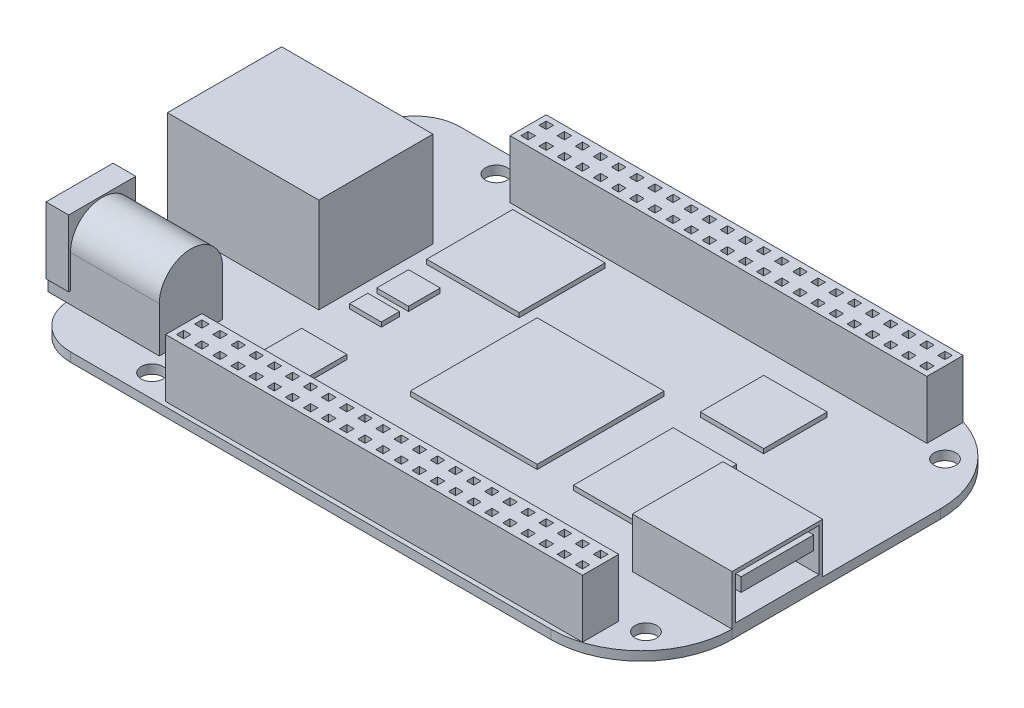
SolidWorks part; units mm, degrees
material "ABS"
ref_plane "Front Plane" through (0, 0, 0) normal (0, 0, 1) x (1, 0, 0)
ref_plane "Top Plane" through (0, 0, 0) normal (0, 1, 0) x (1, 0, 0)
ref_plane "Right Plane" through (0, 0, 0) normal (1, 0, 0) x (0, 0, -1)
sketch "Sketch1" plane through (0, 0, 0) normal (0, 1, 0) x (1, 0, 0)
  line L1 (-12.7, 0) -> (-80.01, 0)
  line L2 (0, 12.7) -> (0, 41.91)
  line L3 (-12.7, 54.61) -> (-80.01, 54.61)
  line L4 (-86.36, 6.35) -> (-86.36, 48.26)
  arc A0 (0, 12.7) -> (-12.7, 0) centre (-12.7, 12.7) cw
  arc A1 (0, 41.91) -> (-12.7, 54.61) centre (-12.7, 41.91) ccw
  arc A2 (-86.36, 6.35) -> (-80.01, 0) centre (-80.01, 6.35) ccw
  arc A3 (-86.36, 48.26) -> (-80.01, 54.61) centre (-80.01, 48.26) cw
  point P7 (0, 0)
  point P10 (0, 54.61)
  point P13 (-86.36, 0)
  dimension "D3" = 12.7
  dimension "D4" = 6.35
  dimension "D1" = 86.36
  dimension "D2" = 54.61
extrude "Boss-Extrude1" add sketch "Sketch1" along normal blind 1.27
sketch "Sketch2" plane through (0, 1.27, 0) normal (0, 1, 0) x (1, 0, 0)
  line L0 (-80.01, 0) -> (-12.7, 0) construction
  line L2 (-71.755, 51.435) -> (-71.755, 3.175) construction
  line L3 (-86.36, 48.26) -> (-86.36, 6.35) construction
  line L4 (-5.715, 48.26) -> (-5.715, 6.35) construction
  circle A0 centre (-71.755, 51.435) radius 1.524
  circle A1 centre (-71.755, 3.175) radius 1.524
  circle A2 centre (-5.715, 48.26) radius 1.524
  circle A3 centre (-5.715, 6.35) radius 1.524
  point P10 (-13.1534, 1.6759)
  point P15 (-61.1926, 0)
  dimension "D7" = 3.048
  dimension "D1" = 48.26
  dimension "D2" = 41.91
  dimension "D3" = 6.35
  dimension "D4" = 14.605
  dimension "D5" = 80.645
  dimension "D6" = 3.175
extrude "Cut-Extrude1" cut sketch "Sketch2" along direction (0, -1, 0) on the side against the normal up to surface (1.27 mm away) up to face at (-44.4387, 0, -27.305)
sketch "Sketch3" plane through (0, 1.27, 0) normal (0, 1, 0) x (1, 0, 0)
  line L0 (-10.16, 48.895) -> (-10.16, 50.165) construction
  line L1 (-67.31, 53.975) -> (-8.89, 53.975)
  line L2 (-67.31, 53.975) -> (-67.31, 48.895)
  line L3 (-67.31, 48.895) -> (-8.89, 48.895)
  line L4 (-8.89, 53.975) -> (-8.89, 48.895)
  line L5 (-86.36, 27.305) -> (0, 27.305) construction
  line L6 (0, 12.7) -> (0, 41.91) construction
  line L7 (-66.548, 4.953) -> (-66.548, 3.937)
  line L8 (-66.548, 4.953) -> (-65.532, 4.953)
  line L9 (-10.16, 50.165) -> (-10.16, 52.705) construction
  line L10 (-10.16, 52.705) -> (-10.16, 53.975) construction
  line L11 (-13.208, 52.197) -> (-12.192, 52.197)
  line L12 (-10.668, 53.213) -> (-9.652, 53.213)
  line L13 (-10.668, 53.213) -> (-10.668, 52.197)
  line L14 (-10.668, 52.197) -> (-9.652, 52.197)
  line L15 (-9.652, 53.213) -> (-9.652, 52.197)
  line L16 (-10.668, 53.213) -> (-9.652, 52.197) construction
  line L17 (-10.668, 52.197) -> (-9.652, 53.213) construction
  line L18 (-10.668, 49.657) -> (-9.652, 49.657)
  line L19 (-10.668, 49.657) -> (-10.668, 50.673)
  line L20 (-10.668, 50.673) -> (-9.652, 50.673)
  line L21 (-9.652, 49.657) -> (-9.652, 50.673)
  line L22 (-10.668, 49.657) -> (-9.652, 50.673) construction
  line L23 (-10.668, 50.673) -> (-9.652, 49.657) construction
  line L24 (-13.208, 53.213) -> (-13.208, 52.197)
  line L25 (-13.208, 53.213) -> (-12.192, 53.213)
  line L26 (-12.192, 53.213) -> (-12.192, 52.197)
  line L27 (-13.208, 50.673) -> (-12.192, 50.673)
  line L28 (-12.192, 49.657) -> (-12.192, 50.673)
  line L29 (-13.208, 49.657) -> (-12.192, 49.657)
  line L30 (-13.208, 49.657) -> (-13.208, 50.673)
  line L31 (-15.748, 52.197) -> (-14.732, 52.197)
  line L32 (-15.748, 53.213) -> (-15.748, 52.197)
  line L33 (-15.748, 53.213) -> (-14.732, 53.213)
  line L34 (-14.732, 53.213) -> (-14.732, 52.197)
  line L35 (-15.748, 50.673) -> (-14.732, 50.673)
  line L36 (-14.732, 49.657) -> (-14.732, 50.673)
  line L37 (-15.748, 49.657) -> (-14.732, 49.657)
  line L38 (-15.748, 49.657) -> (-15.748, 50.673)
  line L39 (-18.288, 52.197) -> (-17.272, 52.197)
  line L40 (-18.288, 53.213) -> (-18.288, 52.197)
  line L41 (-18.288, 53.213) -> (-17.272, 53.213)
  line L42 (-17.272, 53.213) -> (-17.272, 52.197)
  line L43 (-18.288, 50.673) -> (-17.272, 50.673)
  line L44 (-17.272, 49.657) -> (-17.272, 50.673)
  line L45 (-18.288, 49.657) -> (-17.272, 49.657)
  line L46 (-18.288, 49.657) -> (-18.288, 50.673)
  line L47 (-20.828, 52.197) -> (-19.812, 52.197)
  line L48 (-20.828, 53.213) -> (-20.828, 52.197)
  line L49 (-20.828, 53.213) -> (-19.812, 53.213)
  line L50 (-19.812, 53.213) -> (-19.812, 52.197)
  line L51 (-20.828, 50.673) -> (-19.812, 50.673)
  line L52 (-19.812, 49.657) -> (-19.812, 50.673)
  line L53 (-20.828, 49.657) -> (-19.812, 49.657)
  line L54 (-20.828, 49.657) -> (-20.828, 50.673)
  line L55 (-23.368, 52.197) -> (-22.352, 52.197)
  line L56 (-23.368, 53.213) -> (-23.368, 52.197)
  line L57 (-23.368, 53.213) -> (-22.352, 53.213)
  line L58 (-22.352, 53.213) -> (-22.352, 52.197)
  line L59 (-23.368, 50.673) -> (-22.352, 50.673)
  line L60 (-22.352, 49.657) -> (-22.352, 50.673)
  line L61 (-23.368, 49.657) -> (-22.352, 49.657)
  line L62 (-23.368, 49.657) -> (-23.368, 50.673)
  line L63 (-25.908, 52.197) -> (-24.892, 52.197)
  line L64 (-25.908, 53.213) -> (-25.908, 52.197)
  line L65 (-25.908, 53.213) -> (-24.892, 53.213)
  line L66 (-24.892, 53.213) -> (-24.892, 52.197)
  line L67 (-25.908, 50.673) -> (-24.892, 50.673)
  line L68 (-24.892, 49.657) -> (-24.892, 50.673)
  line L69 (-25.908, 49.657) -> (-24.892, 49.657)
  line L70 (-25.908, 49.657) -> (-25.908, 50.673)
  line L71 (-28.448, 52.197) -> (-27.432, 52.197)
  line L72 (-28.448, 53.213) -> (-28.448, 52.197)
  line L73 (-28.448, 53.213) -> (-27.432, 53.213)
  line L74 (-27.432, 53.213) -> (-27.432, 52.197)
  line L75 (-28.448, 50.673) -> (-27.432, 50.673)
  line L76 (-27.432, 49.657) -> (-27.432, 50.673)
  line L77 (-28.448, 49.657) -> (-27.432, 49.657)
  line L78 (-28.448, 49.657) -> (-28.448, 50.673)
  line L79 (-30.988, 52.197) -> (-29.972, 52.197)
  line L80 (-30.988, 53.213) -> (-30.988, 52.197)
  line L81 (-30.988, 53.213) -> (-29.972, 53.213)
  line L82 (-29.972, 53.213) -> (-29.972, 52.197)
  line L83 (-30.988, 50.673) -> (-29.972, 50.673)
  line L84 (-29.972, 49.657) -> (-29.972, 50.673)
  line L85 (-30.988, 49.657) -> (-29.972, 49.657)
  line L86 (-30.988, 49.657) -> (-30.988, 50.673)
  line L87 (-33.528, 52.197) -> (-32.512, 52.197)
  line L88 (-33.528, 53.213) -> (-33.528, 52.197)
  line L89 (-33.528, 53.213) -> (-32.512, 53.213)
  line L90 (-32.512, 53.213) -> (-32.512, 52.197)
  line L91 (-33.528, 50.673) -> (-32.512, 50.673)
  line L92 (-32.512, 49.657) -> (-32.512, 50.673)
  line L93 (-33.528, 49.657) -> (-32.512, 49.657)
  line L94 (-33.528, 49.657) -> (-33.528, 50.673)
  line L95 (-36.068, 52.197) -> (-35.052, 52.197)
  line L96 (-36.068, 53.213) -> (-36.068, 52.197)
  line L97 (-36.068, 53.213) -> (-35.052, 53.213)
  line L98 (-35.052, 53.213) -> (-35.052, 52.197)
  line L99 (-36.068, 50.673) -> (-35.052, 50.673)
  line L100 (-35.052, 49.657) -> (-35.052, 50.673)
  line L101 (-36.068, 49.657) -> (-35.052, 49.657)
  line L102 (-36.068, 49.657) -> (-36.068, 50.673)
  line L103 (-38.608, 52.197) -> (-37.592, 52.197)
  line L104 (-38.608, 53.213) -> (-38.608, 52.197)
  line L105 (-38.608, 53.213) -> (-37.592, 53.213)
  line L106 (-37.592, 53.213) -> (-37.592, 52.197)
  line L107 (-38.608, 50.673) -> (-37.592, 50.673)
  line L108 (-37.592, 49.657) -> (-37.592, 50.673)
  line L109 (-38.608, 49.657) -> (-37.592, 49.657)
  line L110 (-38.608, 49.657) -> (-38.608, 50.673)
  line L111 (-41.148, 52.197) -> (-40.132, 52.197)
  line L112 (-41.148, 53.213) -> (-41.148, 52.197)
  line L113 (-41.148, 53.213) -> (-40.132, 53.213)
  line L114 (-40.132, 53.213) -> (-40.132, 52.197)
  line L115 (-41.148, 50.673) -> (-40.132, 50.673)
  line L116 (-40.132, 49.657) -> (-40.132, 50.673)
  line L117 (-41.148, 49.657) -> (-40.132, 49.657)
  line L118 (-41.148, 49.657) -> (-41.148, 50.673)
  line L119 (-43.688, 52.197) -> (-42.672, 52.197)
  line L120 (-43.688, 53.213) -> (-43.688, 52.197)
  line L121 (-43.688, 53.213) -> (-42.672, 53.213)
  line L122 (-42.672, 53.213) -> (-42.672, 52.197)
  line L123 (-43.688, 50.673) -> (-42.672, 50.673)
  line L124 (-42.672, 49.657) -> (-42.672, 50.673)
  line L125 (-43.688, 49.657) -> (-42.672, 49.657)
  line L126 (-43.688, 49.657) -> (-43.688, 50.673)
  line L127 (-46.228, 52.197) -> (-45.212, 52.197)
  line L128 (-46.228, 53.213) -> (-46.228, 52.197)
  line L129 (-46.228, 53.213) -> (-45.212, 53.213)
  line L130 (-45.212, 53.213) -> (-45.212, 52.197)
  line L131 (-46.228, 50.673) -> (-45.212, 50.673)
  line L132 (-45.212, 49.657) -> (-45.212, 50.673)
  line L133 (-46.228, 49.657) -> (-45.212, 49.657)
  line L134 (-46.228, 49.657) -> (-46.228, 50.673)
  line L135 (-48.768, 52.197) -> (-47.752, 52.197)
  line L136 (-48.768, 53.213) -> (-48.768, 52.197)
  line L137 (-48.768, 53.213) -> (-47.752, 53.213)
  line L138 (-47.752, 53.213) -> (-47.752, 52.197)
  line L139 (-48.768, 50.673) -> (-47.752, 50.673)
  line L140 (-47.752, 49.657) -> (-47.752, 50.673)
  line L141 (-48.768, 49.657) -> (-47.752, 49.657)
  line L142 (-48.768, 49.657) -> (-48.768, 50.673)
  line L143 (-51.308, 52.197) -> (-50.292, 52.197)
  line L144 (-51.308, 53.213) -> (-51.308, 52.197)
  line L145 (-51.308, 53.213) -> (-50.292, 53.213)
  line L146 (-50.292, 53.213) -> (-50.292, 52.197)
  line L147 (-51.308, 50.673) -> (-50.292, 50.673)
  line L148 (-50.292, 49.657) -> (-50.292, 50.673)
  line L149 (-51.308, 49.657) -> (-50.292, 49.657)
  line L150 (-51.308, 49.657) -> (-51.308, 50.673)
  line L151 (-53.848, 52.197) -> (-52.832, 52.197)
  line L152 (-53.848, 53.213) -> (-53.848, 52.197)
  line L153 (-53.848, 53.213) -> (-52.832, 53.213)
  line L154 (-52.832, 53.213) -> (-52.832, 52.197)
  line L155 (-53.848, 50.673) -> (-52.832, 50.673)
  line L156 (-52.832, 49.657) -> (-52.832, 50.673)
  line L157 (-53.848, 49.657) -> (-52.832, 49.657)
  line L158 (-53.848, 49.657) -> (-53.848, 50.673)
  line L159 (-56.388, 52.197) -> (-55.372, 52.197)
  line L160 (-56.388, 53.213) -> (-56.388, 52.197)
  line L161 (-56.388, 53.213) -> (-55.372, 53.213)
  line L162 (-55.372, 53.213) -> (-55.372, 52.197)
  line L163 (-56.388, 50.673) -> (-55.372, 50.673)
  line L164 (-55.372, 49.657) -> (-55.372, 50.673)
  line L165 (-56.388, 49.657) -> (-55.372, 49.657)
  line L166 (-56.388, 49.657) -> (-56.388, 50.673)
  line L167 (-58.928, 52.197) -> (-57.912, 52.197)
  line L168 (-58.928, 53.213) -> (-58.928, 52.197)
  line L169 (-58.928, 53.213) -> (-57.912, 53.213)
  line L170 (-57.912, 53.213) -> (-57.912, 52.197)
  line L171 (-58.928, 50.673) -> (-57.912, 50.673)
  line L172 (-57.912, 49.657) -> (-57.912, 50.673)
  line L173 (-58.928, 49.657) -> (-57.912, 49.657)
  line L174 (-58.928, 49.657) -> (-58.928, 50.673)
  line L175 (-61.468, 52.197) -> (-60.452, 52.197)
  line L176 (-61.468, 53.213) -> (-61.468, 52.197)
  line L177 (-61.468, 53.213) -> (-60.452, 53.213)
  line L178 (-60.452, 53.213) -> (-60.452, 52.197)
  line L179 (-61.468, 50.673) -> (-60.452, 50.673)
  line L180 (-60.452, 49.657) -> (-60.452, 50.673)
  line L181 (-61.468, 49.657) -> (-60.452, 49.657)
  line L182 (-61.468, 49.657) -> (-61.468, 50.673)
  line L183 (-64.008, 52.197) -> (-62.992, 52.197)
  line L184 (-64.008, 53.213) -> (-64.008, 52.197)
  line L185 (-64.008, 53.213) -> (-62.992, 53.213)
  line L186 (-62.992, 53.213) -> (-62.992, 52.197)
  line L187 (-64.008, 50.673) -> (-62.992, 50.673)
  line L188 (-62.992, 49.657) -> (-62.992, 50.673)
  line L189 (-64.008, 49.657) -> (-62.992, 49.657)
  line L190 (-64.008, 49.657) -> (-64.008, 50.673)
  line L191 (-66.548, 52.197) -> (-65.532, 52.197)
  line L192 (-66.548, 53.213) -> (-66.548, 52.197)
  line L193 (-66.548, 53.213) -> (-65.532, 53.213)
  line L194 (-65.532, 53.213) -> (-65.532, 52.197)
  line L195 (-66.548, 50.673) -> (-65.532, 50.673)
  line L196 (-65.532, 49.657) -> (-65.532, 50.673)
  line L197 (-66.548, 49.657) -> (-65.532, 49.657)
  line L198 (-66.548, 49.657) -> (-66.548, 50.673)
  line L199 (-66.548, 49.657) -> (-65.532, 50.673) construction
  line L200 (-86.36, 48.26) -> (-86.36, 6.35) construction
  line L201 (-65.532, 4.953) -> (-65.532, 3.937)
  line L202 (-12.7, 54.61) -> (-80.01, 54.61) construction
  line L203 (-66.548, 3.937) -> (-65.532, 3.937)
  line L204 (-65.532, 1.397) -> (-65.532, 2.413)
  line L205 (-66.548, 1.397) -> (-65.532, 1.397)
  line L206 (-66.548, 1.397) -> (-66.548, 2.413)
  line L207 (-66.548, 2.413) -> (-65.532, 2.413)
  line L208 (-64.008, 4.953) -> (-64.008, 3.937)
  line L209 (-64.008, 4.953) -> (-62.992, 4.953)
  line L210 (-62.992, 4.953) -> (-62.992, 3.937)
  line L211 (-64.008, 3.937) -> (-62.992, 3.937)
  line L212 (-62.992, 1.397) -> (-62.992, 2.413)
  line L213 (-64.008, 1.397) -> (-62.992, 1.397)
  line L214 (-64.008, 1.397) -> (-64.008, 2.413)
  line L215 (-64.008, 2.413) -> (-62.992, 2.413)
  line L216 (-61.468, 4.953) -> (-61.468, 3.937)
  line L217 (-61.468, 4.953) -> (-60.452, 4.953)
  line L218 (-60.452, 4.953) -> (-60.452, 3.937)
  line L219 (-61.468, 3.937) -> (-60.452, 3.937)
  line L220 (-60.452, 1.397) -> (-60.452, 2.413)
  line L221 (-61.468, 1.397) -> (-60.452, 1.397)
  line L222 (-61.468, 1.397) -> (-61.468, 2.413)
  line L223 (-61.468, 2.413) -> (-60.452, 2.413)
  line L224 (-58.928, 4.953) -> (-58.928, 3.937)
  line L225 (-58.928, 4.953) -> (-57.912, 4.953)
  line L226 (-57.912, 4.953) -> (-57.912, 3.937)
  line L227 (-58.928, 3.937) -> (-57.912, 3.937)
  line L228 (-57.912, 1.397) -> (-57.912, 2.413)
  line L229 (-58.928, 1.397) -> (-57.912, 1.397)
  line L230 (-58.928, 1.397) -> (-58.928, 2.413)
  line L231 (-58.928, 2.413) -> (-57.912, 2.413)
  line L232 (-56.388, 4.953) -> (-56.388, 3.937)
  line L233 (-56.388, 4.953) -> (-55.372, 4.953)
  line L234 (-55.372, 4.953) -> (-55.372, 3.937)
  line L235 (-56.388, 3.937) -> (-55.372, 3.937)
  line L236 (-55.372, 1.397) -> (-55.372, 2.413)
  line L237 (-56.388, 1.397) -> (-55.372, 1.397)
  line L238 (-56.388, 1.397) -> (-56.388, 2.413)
  line L239 (-56.388, 2.413) -> (-55.372, 2.413)
  line L240 (-53.848, 4.953) -> (-53.848, 3.937)
  line L241 (-53.848, 4.953) -> (-52.832, 4.953)
  line L242 (-52.832, 4.953) -> (-52.832, 3.937)
  line L243 (-53.848, 3.937) -> (-52.832, 3.937)
  line L244 (-52.832, 1.397) -> (-52.832, 2.413)
  line L245 (-53.848, 1.397) -> (-52.832, 1.397)
  line L246 (-53.848, 1.397) -> (-53.848, 2.413)
  line L247 (-53.848, 2.413) -> (-52.832, 2.413)
  line L248 (-51.308, 4.953) -> (-51.308, 3.937)
  line L249 (-51.308, 4.953) -> (-50.292, 4.953)
  line L250 (-50.292, 4.953) -> (-50.292, 3.937)
  line L251 (-51.308, 3.937) -> (-50.292, 3.937)
  line L252 (-50.292, 1.397) -> (-50.292, 2.413)
  line L253 (-51.308, 1.397) -> (-50.292, 1.397)
  line L254 (-51.308, 1.397) -> (-51.308, 2.413)
  line L255 (-51.308, 2.413) -> (-50.292, 2.413)
  line L256 (-48.768, 4.953) -> (-48.768, 3.937)
  line L257 (-48.768, 4.953) -> (-47.752, 4.953)
  line L258 (-47.752, 4.953) -> (-47.752, 3.937)
  line L259 (-48.768, 3.937) -> (-47.752, 3.937)
  line L260 (-47.752, 1.397) -> (-47.752, 2.413)
  line L261 (-48.768, 1.397) -> (-47.752, 1.397)
  line L262 (-48.768, 1.397) -> (-48.768, 2.413)
  line L263 (-48.768, 2.413) -> (-47.752, 2.413)
  line L264 (-46.228, 4.953) -> (-46.228, 3.937)
  line L265 (-46.228, 4.953) -> (-45.212, 4.953)
  line L266 (-45.212, 4.953) -> (-45.212, 3.937)
  line L267 (-46.228, 3.937) -> (-45.212, 3.937)
  line L268 (-45.212, 1.397) -> (-45.212, 2.413)
  line L269 (-46.228, 1.397) -> (-45.212, 1.397)
  line L270 (-46.228, 1.397) -> (-46.228, 2.413)
  line L271 (-46.228, 2.413) -> (-45.212, 2.413)
  line L272 (-43.688, 4.953) -> (-43.688, 3.937)
  line L273 (-43.688, 4.953) -> (-42.672, 4.953)
  line L274 (-42.672, 4.953) -> (-42.672, 3.937)
  line L275 (-43.688, 3.937) -> (-42.672, 3.937)
  line L276 (-42.672, 1.397) -> (-42.672, 2.413)
  line L277 (-43.688, 1.397) -> (-42.672, 1.397)
  line L278 (-43.688, 1.397) -> (-43.688, 2.413)
  line L279 (-43.688, 2.413) -> (-42.672, 2.413)
  line L280 (-41.148, 4.953) -> (-41.148, 3.937)
  line L281 (-41.148, 4.953) -> (-40.132, 4.953)
  line L282 (-40.132, 4.953) -> (-40.132, 3.937)
  line L283 (-41.148, 3.937) -> (-40.132, 3.937)
  line L284 (-40.132, 1.397) -> (-40.132, 2.413)
  line L285 (-41.148, 1.397) -> (-40.132, 1.397)
  line L286 (-41.148, 1.397) -> (-41.148, 2.413)
  line L287 (-41.148, 2.413) -> (-40.132, 2.413)
  line L288 (-38.608, 4.953) -> (-38.608, 3.937)
  line L289 (-38.608, 4.953) -> (-37.592, 4.953)
  line L290 (-37.592, 4.953) -> (-37.592, 3.937)
  line L291 (-38.608, 3.937) -> (-37.592, 3.937)
  line L292 (-37.592, 1.397) -> (-37.592, 2.413)
  line L293 (-38.608, 1.397) -> (-37.592, 1.397)
  line L294 (-38.608, 1.397) -> (-38.608, 2.413)
  line L295 (-38.608, 2.413) -> (-37.592, 2.413)
  line L296 (-36.068, 4.953) -> (-36.068, 3.937)
  line L297 (-36.068, 4.953) -> (-35.052, 4.953)
  line L298 (-35.052, 4.953) -> (-35.052, 3.937)
  line L299 (-36.068, 3.937) -> (-35.052, 3.937)
  line L300 (-35.052, 1.397) -> (-35.052, 2.413)
  line L301 (-36.068, 1.397) -> (-35.052, 1.397)
  line L302 (-36.068, 1.397) -> (-36.068, 2.413)
  line L303 (-36.068, 2.413) -> (-35.052, 2.413)
  line L304 (-33.528, 4.953) -> (-33.528, 3.937)
  line L305 (-33.528, 4.953) -> (-32.512, 4.953)
  line L306 (-32.512, 4.953) -> (-32.512, 3.937)
  line L307 (-33.528, 3.937) -> (-32.512, 3.937)
  line L308 (-32.512, 1.397) -> (-32.512, 2.413)
  line L309 (-33.528, 1.397) -> (-32.512, 1.397)
  line L310 (-33.528, 1.397) -> (-33.528, 2.413)
  line L311 (-33.528, 2.413) -> (-32.512, 2.413)
  line L312 (-30.988, 4.953) -> (-30.988, 3.937)
  line L313 (-30.988, 4.953) -> (-29.972, 4.953)
  line L314 (-29.972, 4.953) -> (-29.972, 3.937)
  line L315 (-30.988, 3.937) -> (-29.972, 3.937)
  line L316 (-29.972, 1.397) -> (-29.972, 2.413)
  line L317 (-30.988, 1.397) -> (-29.972, 1.397)
  line L318 (-30.988, 1.397) -> (-30.988, 2.413)
  line L319 (-30.988, 2.413) -> (-29.972, 2.413)
  line L320 (-28.448, 4.953) -> (-28.448, 3.937)
  line L321 (-28.448, 4.953) -> (-27.432, 4.953)
  line L322 (-27.432, 4.953) -> (-27.432, 3.937)
  line L323 (-28.448, 3.937) -> (-27.432, 3.937)
  line L324 (-27.432, 1.397) -> (-27.432, 2.413)
  line L325 (-28.448, 1.397) -> (-27.432, 1.397)
  line L326 (-28.448, 1.397) -> (-28.448, 2.413)
  line L327 (-28.448, 2.413) -> (-27.432, 2.413)
  line L328 (-25.908, 4.953) -> (-25.908, 3.937)
  line L329 (-25.908, 4.953) -> (-24.892, 4.953)
  line L330 (-24.892, 4.953) -> (-24.892, 3.937)
  line L331 (-25.908, 3.937) -> (-24.892, 3.937)
  line L332 (-24.892, 1.397) -> (-24.892, 2.413)
  line L333 (-25.908, 1.397) -> (-24.892, 1.397)
  line L334 (-25.908, 1.397) -> (-25.908, 2.413)
  line L335 (-25.908, 2.413) -> (-24.892, 2.413)
  line L336 (-23.368, 4.953) -> (-23.368, 3.937)
  line L337 (-23.368, 4.953) -> (-22.352, 4.953)
  line L338 (-22.352, 4.953) -> (-22.352, 3.937)
  line L339 (-23.368, 3.937) -> (-22.352, 3.937)
  line L340 (-22.352, 1.397) -> (-22.352, 2.413)
  line L341 (-23.368, 1.397) -> (-22.352, 1.397)
  line L342 (-23.368, 1.397) -> (-23.368, 2.413)
  line L343 (-23.368, 2.413) -> (-22.352, 2.413)
  line L344 (-20.828, 4.953) -> (-20.828, 3.937)
  line L345 (-20.828, 4.953) -> (-19.812, 4.953)
  line L346 (-19.812, 4.953) -> (-19.812, 3.937)
  line L347 (-20.828, 3.937) -> (-19.812, 3.937)
  line L348 (-19.812, 1.397) -> (-19.812, 2.413)
  line L349 (-20.828, 1.397) -> (-19.812, 1.397)
  line L350 (-20.828, 1.397) -> (-20.828, 2.413)
  line L351 (-20.828, 2.413) -> (-19.812, 2.413)
  line L352 (-18.288, 4.953) -> (-18.288, 3.937)
  line L353 (-18.288, 4.953) -> (-17.272, 4.953)
  line L354 (-17.272, 4.953) -> (-17.272, 3.937)
  line L355 (-18.288, 3.937) -> (-17.272, 3.937)
  line L356 (-17.272, 1.397) -> (-17.272, 2.413)
  line L357 (-18.288, 1.397) -> (-17.272, 1.397)
  line L358 (-18.288, 1.397) -> (-18.288, 2.413)
  line L359 (-18.288, 2.413) -> (-17.272, 2.413)
  line L360 (-15.748, 4.953) -> (-15.748, 3.937)
  line L361 (-15.748, 4.953) -> (-14.732, 4.953)
  line L362 (-14.732, 4.953) -> (-14.732, 3.937)
  line L363 (-15.748, 3.937) -> (-14.732, 3.937)
  line L364 (-14.732, 1.397) -> (-14.732, 2.413)
  line L365 (-15.748, 1.397) -> (-14.732, 1.397)
  line L366 (-15.748, 1.397) -> (-15.748, 2.413)
  line L367 (-15.748, 2.413) -> (-14.732, 2.413)
  line L368 (-13.208, 4.953) -> (-13.208, 3.937)
  line L369 (-13.208, 4.953) -> (-12.192, 4.953)
  line L370 (-12.192, 4.953) -> (-12.192, 3.937)
  line L371 (-13.208, 3.937) -> (-12.192, 3.937)
  line L372 (-12.192, 1.397) -> (-12.192, 2.413)
  line L373 (-13.208, 1.397) -> (-12.192, 1.397)
  line L374 (-13.208, 1.397) -> (-13.208, 2.413)
  line L375 (-9.652, 4.953) -> (-9.652, 3.937)
  line L376 (-10.668, 3.937) -> (-9.652, 3.937)
  line L377 (-10.668, 4.953) -> (-10.668, 3.937)
  line L378 (-10.668, 4.953) -> (-9.652, 4.953)
  line L379 (-9.652, 1.397) -> (-9.652, 2.413)
  line L380 (-10.668, 2.413) -> (-9.652, 2.413)
  line L381 (-10.668, 1.397) -> (-10.668, 2.413)
  line L382 (-10.668, 1.397) -> (-9.652, 1.397)
  line L383 (-13.208, 2.413) -> (-12.192, 2.413)
  line L384 (-8.89, 0.635) -> (-8.89, 5.715)
  line L385 (-67.31, 5.715) -> (-8.89, 5.715)
  line L386 (-67.31, 0.635) -> (-67.31, 5.715)
  line L387 (-67.31, 0.635) -> (-8.89, 0.635)
  circle A0 centre (-66.04, 50.165) radius 0.1361
  dimension "D1" = 1.016
  dimension "D2" = 2.54
  dimension "D3" = 5.08
  dimension "D4" = 58.42
  dimension "D5" = 1.27
  dimension "D7" = 20.32
  dimension "D8" = 0.635
  dimension "D6" = 23
extrude "Boss-Extrude2" add sketch "Sketch3" along normal blind 8.128 contours L4 L1 L2 L3 L193 L194 L191 L192 L185 L186 L183 L184 L177 L178 L175 L176 L169 L170 L167 L168 L161 L162 L159 L160 L153 L154 L151 L152 L145 L146 L143 L144 L137 L138 L135 L136 L129 L130 L127 L128 L121 | L386 L387 L384 L385 L374 L383 L372 L373 L382 L381 L380 L379 L366 L367 L364 L365 L363 L360 L361 L362 L350 L351 L348 L349 L347 L344 L345 L346 L334 L335 L332 L333 L331 L328 L329 L330 L318 L319 L316 L317 L315 region at (-38.1, 1.27, -51.435) region at (-38.1, 1.27, -3.175)
sketch "Sketch4" plane through (0, 1.27, 0) normal (0, 1, 0) x (1, 0, 0)
  line L0 (-86.36, 48.26) -> (-86.36, 6.35) construction
  line L1 (-67.691, 22.479) -> (-88.9, 22.479)
  line L2 (-67.691, 22.479) -> (-67.691, 38.481)
  line L3 (-67.691, 38.481) -> (-88.9, 38.481)
  line L4 (-88.9, 22.479) -> (-88.9, 38.481)
  line L5 (-12.7, 54.61) -> (-80.01, 54.61) construction
  dimension "D1" = 2.54
  dimension "D2" = 21.209
  dimension "D3" = 16.002
  dimension "D4" = 16.129
extrude "Boss-Extrude3" add sketch "Sketch4" along normal blind 13.335
sketch "Sketch5" plane through (-88.9, 0, 0) normal (-1, 0, 0) x (0, 0, 1)
  line L0 (-30.48, 2.286) -> (-30.48, 3.937) construction
  line L1 (-36.83, 12.065) -> (-24.13, 12.065)
  line L2 (-36.83, 12.065) -> (-36.83, 5.461)
  line L3 (-36.83, 5.461) -> (-24.13, 5.461)
  line L4 (-24.13, 12.065) -> (-24.13, 5.461)
  line L5 (-33.655, 5.461) -> (-27.305, 5.461)
  line L6 (-33.655, 5.461) -> (-33.655, 3.937)
  line L7 (-33.655, 3.937) -> (-27.305, 3.937)
  line L8 (-27.305, 5.461) -> (-27.305, 3.937)
  line L9 (-32.512, 3.937) -> (-28.448, 3.937)
  line L10 (-32.512, 3.937) -> (-32.512, 2.286)
  line L11 (-32.512, 2.286) -> (-28.448, 2.286)
  line L12 (-28.448, 3.937) -> (-28.448, 2.286)
  line L13 (-30.48, 3.937) -> (-30.48, 5.461) construction
  line L14 (-38.481, 14.605) -> (-22.479, 14.605) construction
  line L15 (-36.83, 12.065) -> (-38.481, 12.065) construction
  line L16 (-38.481, 14.605) -> (-38.481, 1.27) construction
  line L17 (-24.13, 12.065) -> (-22.479, 12.065) construction
  line L18 (-22.479, 14.605) -> (-22.479, 1.27) construction
  dimension "D1" = 12.7
  dimension "D2" = 6.604
  dimension "D3" = 2.54
  dimension "D4" = 1.524
  dimension "D5" = 1.651
  dimension "D6" = 4.064
  dimension "D7" = 6.35
extrude "Cut-Extrude2" cut sketch "Sketch5" against normal blind 17.78 contours L4 L1 L2 L3 | L8 L3 L6 L7 | L12 L7 L10 L11 region at (-88.9, 8.763, -30.48) region at (-88.9, 4.699, -30.48) region at (-88.9, 3.1115, -30.48)
sketch "Sketch6" plane through (0, 1.27, 0) normal (0, 1, 0) x (1, 0, 0)
  line L0 (-67.31, 48.895) -> (-8.89, 48.895) construction
  line L1 (-65.659, 35.56) -> (-52.705, 35.56)
  line L2 (-65.659, 35.56) -> (-65.659, 47.625)
  line L3 (-65.659, 47.625) -> (-52.705, 47.625)
  line L4 (-52.705, 35.56) -> (-52.705, 47.625)
  line L5 (-50.8, 36.195) -> (-33.02, 36.195)
  line L6 (-50.8, 36.195) -> (-50.8, 18.415)
  line L7 (-50.8, 18.415) -> (-33.02, 18.415)
  line L8 (-33.02, 36.195) -> (-33.02, 18.415)
  line L9 (-27.94, 45.085) -> (-19.05, 45.085)
  line L10 (-27.94, 45.085) -> (-27.94, 36.195)
  line L11 (-27.94, 36.195) -> (-19.05, 36.195)
  line L12 (-19.05, 45.085) -> (-19.05, 36.195)
  line L13 (-27.94, 32.385) -> (-19.05, 32.385)
  line L14 (-27.94, 32.385) -> (-27.94, 18.415)
  line L15 (-27.94, 18.415) -> (-19.05, 18.415)
  line L16 (-19.05, 32.385) -> (-19.05, 18.415)
  line L17 (-66.04, 18.415) -> (-59.69, 18.415)
  line L18 (-66.04, 18.415) -> (-66.04, 12.065)
  line L19 (-66.04, 12.065) -> (-59.69, 12.065)
  line L20 (-59.69, 18.415) -> (-59.69, 12.065)
  line L21 (-65.659, 27.305) -> (-61.214, 27.305)
  line L22 (-65.659, 27.305) -> (-65.659, 24.765)
  line L23 (-65.659, 24.765) -> (-61.214, 24.765)
  line L24 (-61.214, 27.305) -> (-61.214, 24.765)
  line L25 (-65.659, 33.02) -> (-61.214, 33.02)
  line L26 (-65.659, 33.02) -> (-65.659, 28.575)
  line L27 (-65.659, 28.575) -> (-61.214, 28.575)
  line L28 (-61.214, 33.02) -> (-61.214, 28.575)
  line L29 (0, 12.7) -> (0, 41.91) construction
  line L30 (-67.31, 48.895) -> (-8.89, 48.895) construction
  line L31 (-67.31, 5.715) -> (-8.89, 5.715) construction
  line L33 (-67.31, 0.635) -> (-67.31, 5.715) construction
  dimension "D1" = 8.89
  dimension "D2" = 13.97
  dimension "D3" = 3.81
  dimension "D4" = 3.81
  dimension "D5" = 19.05
  dimension "D6" = 17.78
  dimension "D7" = 12.7
  dimension "D8" = 33.02
  dimension "D9" = 12.954
  dimension "D10" = 12.065
  dimension "D11" = 1.905
  dimension "D12" = 4.445
  dimension "D13" = 2.54
  dimension "D14" = 1.27
  dimension "D15" = 2.54
  dimension "D16" = 1.27
  dimension "D17" = 6.35
  dimension "D18" = 6.35
  dimension "D19" = 1.27
extrude "Boss-Extrude4" add sketch "Sketch6" along normal blind 0.635
sketch "Sketch7" plane through (0, 1.27, 0) normal (0, 1, 0) x (1, 0, 0)
  line L1 (0, 12.7) -> (-13.97, 12.7)
  line L2 (0, 12.7) -> (0, 25.4)
  line L3 (0, 25.4) -> (-13.97, 25.4)
  line L4 (-13.97, 12.7) -> (-13.97, 25.4)
  line L5 (-80.01, 0) -> (-12.7, 0) construction
  line L6 (0, 12.7) -> (0, 41.91) construction
  dimension "D1" = 12.7
  dimension "D2" = 13.97
  dimension "D3" = 25.4
extrude "Boss-Extrude5" add sketch "Sketch7" along normal blind 6.985
sketch "Sketch8" plane through (0, 0, 0) normal (1, 0, 0) x (0, 0, -1)
  line L0 (12.7, 8.255) -> (25.4, 8.255) construction
  line L1 (13.97, 6.985) -> (24.13, 6.985)
  line L2 (13.97, 6.985) -> (13.97, 5.08)
  line L3 (13.97, 5.08) -> (24.13, 5.08)
  line L4 (24.13, 6.985) -> (24.13, 5.08)
  line L5 (13.208, 7.747) -> (24.892, 7.747)
  line L6 (13.208, 7.747) -> (13.208, 1.778)
  line L7 (13.208, 1.778) -> (24.892, 1.778)
  line L8 (24.892, 7.747) -> (24.892, 1.778)
  line L9 (25.4, 8.255) -> (25.4, 1.27) construction
  line L10 (12.7, 8.255) -> (12.7, 1.27) construction
  line L11 (12.7, 1.27) -> (0, 1.27) construction
  line L12 (13.97, 7.18) -> (13.208, 7.18) construction
  line L14 (24.892, 6.9479) -> (24.13, 6.9479) construction
  dimension "D1" = 0.508
  dimension "D2" = 0.508
  dimension "D3" = 0.508
  dimension "D4" = 0.508
  dimension "D5" = 1.905
  dimension "D6" = 10.16
  dimension "D7" = 3.175
extrude "Cut-Extrude3" cut sketch "Sketch8" against normal blind 12.7
sketch "Sketch9" plane through (0, 1.27, 0) normal (0, 1, 0) x (1, 0, 0)
  line L0 (-88.9, 38.481) -> (-88.9, 22.479) construction
  line L1 (-73.279, 5.715) -> (-88.9, 5.715)
  line L2 (-73.279, 5.715) -> (-73.279, 14.605)
  line L3 (-73.279, 14.605) -> (-88.9, 14.605)
  line L4 (-88.9, 5.715) -> (-88.9, 14.605)
  line L5 (-67.31, 5.715) -> (-8.89, 5.715) construction
  circle A0 centre (-71.755, 3.175) radius 1.524 construction
  dimension "D1" = 8.89
extrude "Boss-Extrude6" add sketch "Sketch9" along normal blind 6.35
sketch "Sketch10" plane through (-88.9, 0, 0) normal (-1, 0, 0) x (0, 0, 1)
  line L0 (-14.605, 7.62) -> (-5.715, 7.62) construction
  circle A0 centre (-10.16, 7.62) radius 4.445
  circle A1 centre (-10.16, 7.62) radius 3.4925
  circle A2 centre (-10.16, 7.62) radius 0.635
  line M3 (-5.715, 7.62) -> (-14.605, 7.62)
  dimension "D1" = 1.27
  dimension "D2" = 6.985
extrude "Boss-Extrude7" add sketch "Sketch10" along direction (1, 0, 0) on the side against the normal up to surface (15.621 mm away) contours A1 A0 M3 | A1 A0 M3 | A2 M3 | A2 A1 M3 region at (-88.9, 7.7194, -6.1912) region at (-88.9, 3.2744, -10.16) region at (-88.9, 9.1437, -10.16) region at (-88.9, 7.8895, -10.16) up to face at (-73.279, 4.445, -10.16)
sketch "Sketch11" plane through (-88.9, 0, 0) normal (-1, 0, 0) x (0, 0, 1)
  line L0 (-14.605, 7.62) -> (-14.605, 1.27) construction
  line L1 (-5.461, 2.952) -> (-14.859, 2.952)
  line L2 (-5.461, 2.952) -> (-5.461, 12.288)
  line L3 (-5.461, 12.288) -> (-14.859, 12.288)
  line L4 (-14.859, 2.952) -> (-14.859, 12.288)
  line L5 (-5.461, 2.952) -> (-14.859, 12.288) construction
  line L6 (-5.461, 12.288) -> (-14.859, 2.952) construction
  point P0 (-10.16, 7.62)
  dimension "D1" = 0.254
extrude "Boss-Extrude8" add sketch "Sketch11" against normal blind 3.175
extrude "Cut-Extrude4" cut sketch "Sketch10<3>" against normal blind 12.7 contours A2 A1 M3 | A2 A1 M3 region at (-88.9, 9.1437, -10.16) region at (-88.9, 6.0963, -10.16)
sketch "Sketch10<3>" plane through (-88.9, 0, 0) normal (-1, 0, 0) x (0, 0, 1) same geometry as "Sketch10"
fillet "Fillet1" radius 0.635 1 edges at (-88.9, 7.62, -9.525)
